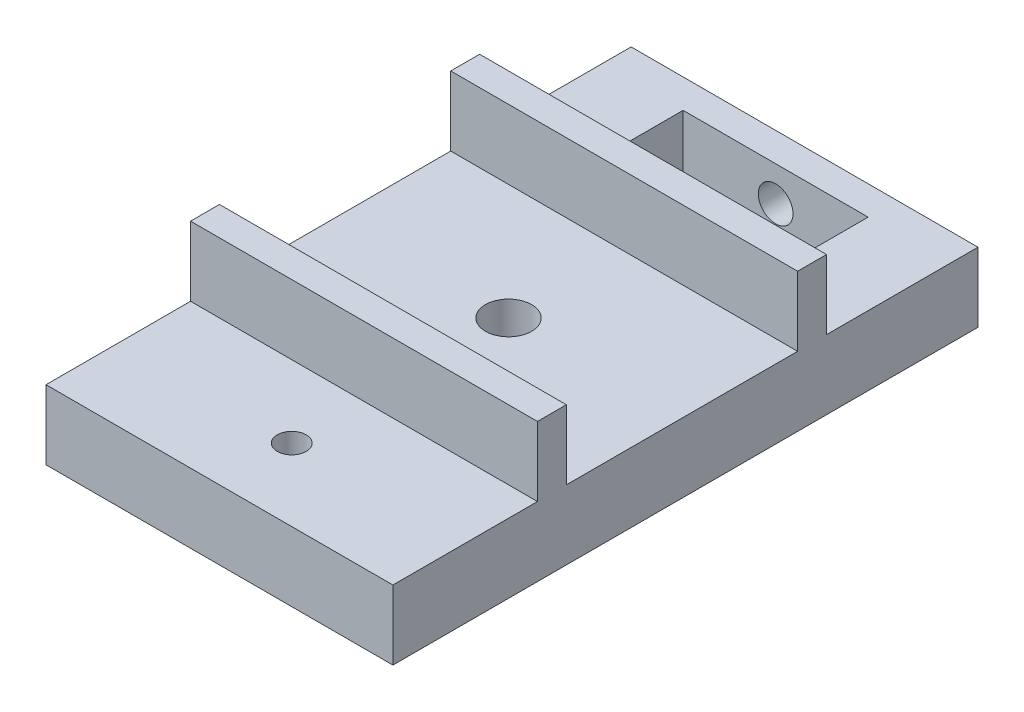
SolidWorks part; units mm, degrees
ref_plane "Front" through (0, 0, 0) normal (0, 0, 1) x (1, 0, 0)
ref_plane "Top" through (0, 0, 0) normal (0, 1, 0) x (1, 0, 0)
ref_plane "Right" through (0, 0, 0) normal (1, 0, 0) x (0, 0, -1)
sketch "Sketch1" plane through (0, 0, 0) normal (0, 1, 0) x (1, 0, 0)
  line L0 (0, -20) -> (0, -22.5)
  line L1 (0, 0) -> (-30, 0)
  line L2 (0, 0) -> (0, -20)
  line L3 (0, -20) -> (-30, -20)
  line L4 (-30, 0) -> (-30, -20)
  line L5 (0, -22.5) -> (-30, -22.5)
  line L6 (-30, -22.5) -> (-30, -20)
  line L7 (0, 0) -> (-7, 0)
  line L8 (-30, 0) -> (0, 0)
  line L9 (-30, 0) -> (-30, 2.5)
  line L10 (-30, 2.5) -> (0, 2.5)
  line L11 (0, 0) -> (0, 2.5)
  line L12 (-30, 0) -> (-23, 0)
  line L13 (-30, 2.5) -> (-30, 13.1)
  line L14 (-30, 13.1) -> (0, 13.1)
  line L15 (0, 13.1) -> (0, 2.5)
  line L16 (0, 13.1) -> (0, 15.6)
  line L17 (0, 15.6) -> (-30, 15.6)
  line L18 (-30, 15.6) -> (-30, 13.1)
  line L19 (-7, 0) -> (-7, 15.6)
  line L20 (-23, 0) -> (-23, 15.6)
  dimension "D1" = 20
  dimension "D2" = 2.5
  dimension "D3" = 2.5
  dimension "D4" = 30
  dimension "D5" = 7
  dimension "D6" = 7
  dimension "D7" = 10.6
  dimension "D8" = 2.5
extrude "Boss-Extrude1" add sketch "Sketch1" along normal blind 6 contours L1 L8 L4 L3 L2 | L6 L5 L0 L3 | L20 L1 L19 L10 | L19 L1 L11 L10 | L19 L10 L15 L14 | L19 L14 L16 L17 | L20 L14 L19 L17 | L14 L20 L17 L18 | L10 L20 L14 L13 | L8 L20 L10 L9 region at (-15, 0, 10) region at (-15, 0, 21.25) region at (-3.5, 0, -1.25) region at (-15, 0, -1.25) region at (-3.5, 0, -7.8) region at (-26.5, 0, -1.25) region at (-3.5, 0, -14.35) region at (-26.5, 0, -7.8) region at (-15, 0, -14.35) region at (-26.5, 0, -14.35)
extrude "Boss-Extrude2" add sketch "Sketch1<3>" along normal blind 12 contours L19 L1 L11 L10 | L20 L1 L19 L10 | L6 L5 L0 L3 | L8 L20 L10 L9 region at (-15, 0, 21.25) region at (-3.5, 0, -1.25) region at (-15, 0, -1.25) region at (-26.5, 0, -1.25)
sketch "Sketch1<3>" plane through (0, 0, 0) normal (0, 1, 0) x (1, 0, 0) same geometry as "Sketch1"
sketch "Sketch3" plane through (0, 0, -15.6) normal (0, 0, -1) x (-1, 0, 0)
  line L0 (30, 3) -> (23, 3)
  line L1 (30, 6) -> (30, 0) construction
  line L2 (23, 3) -> (15, 3)
  circle A0 centre (15, 3) radius 1.5
  dimension "D1" = 7
  dimension "D2" = 8
extrude "Cut-Extrude2" cut sketch "Sketch3" against normal blind 5 contours A0
sketch "Sketch4" plane through (0, 0, -2.5) normal (0, 0, -1) x (-1, 0, 0)
  line L0 (23, 3) -> (15, 3)
  line L1 (23, 6) -> (23, 0) construction
  line L3 (17.8868, 3) -> (16.4434, 5.5)
  line L4 (16.4434, 5.5) -> (13.5566, 5.5)
  line L5 (13.5566, 5.5) -> (12.1132, 3)
  line L6 (12.1132, 3) -> (13.5566, 0.5)
  line L7 (13.5566, 0.5) -> (16.4434, 0.5)
  line L8 (16.4434, 0.5) -> (17.8868, 3)
  circle A0 centre (15, 3) radius 2.5 construction
  dimension "D1" = 8
extrude "Cut-Extrude3" cut sketch "Sketch4" against normal blind 2.5 contours L7 L8 L3 L4 L5 L6 region at (-17.0989, 1.7882, -2.5)
ref_plane "Plane1" through (0, 0, 10) normal (0, 0, -1) x (-1, 0, 0)
sketch "Sketch2" plane through (0, 6, 0) normal (0, 1, 0) x (1, 0, 0)
  line L0 (-30, -10) -> (0, -10)
  line L1 (-30, 0) -> (-30, -20) construction
  line L2 (0, 0) -> (0, -20) construction
  circle A0 centre (-15, -10) radius 2
extrude "Cut-Extrude1" cut sketch "Sketch2" against normal through all contours L0 A0 | L0 A0 region at (-15, 6, 9.1512) region at (-15, 6, 10.8488)
sketch "Sketch5" plane through (0, 0, 0) normal (0, -1, 0) x (1, 0, 0)
  line L0 (-30, 22.5) -> (-25, 22.5)
  line L1 (-30, 22.5) -> (0, 22.5)
  line L2 (-30, 22.5) -> (-30, 32.5)
  line L3 (0, 22.5) -> (0, 32.5)
  line L4 (-30, 32.5) -> (0, 32.5)
  line L5 (-25, 22.5) -> (-25, 32.5)
  line L6 (-25, 32.5) -> (-5, 32.5)
  line L7 (-5, 32.5) -> (-5, 22.5)
  line L8 (-5, 22.5) -> (0, 22.5)
  line L9 (-30, 32.5) -> (-30, 35)
  line L10 (-30, 35) -> (0, 35)
  line L11 (0, 35) -> (0, 32.5)
  line L12 (-15, 35) -> (-15, 22.5)
  circle A0 centre (-15, 28.75) radius 1.25
  line M7 (0, 22.5) -> (-30, 22.5)
  dimension "D1" = 10
  dimension "D2" = 5
  dimension "D3" = 5
  dimension "D4" = 2.5
extrude "Boss-Extrude3" add sketch "Sketch5" against normal blind 6 contours L5 L4 L2 M7 | L11 L10 L9 L4 | L4 L7 L3 M7 | L7 L4 L5 L1 | A0 L12 L4 L5 M7 | L12 L10 L9 L4 region at (-27.5, 0, 27.5) region at (-20.1125, 0, 27.4685) region at (-22.5, 0, 33.75) region at (-9.8875, 0, 27.4685) region at (-2.5, 0, 27.5) region at (-7.5, 0, 33.75)
sketch "Sketch6" plane through (0, 0, 35) normal (0, 0, 1) x (1, 0, 0)
  line L0 (0, 0) -> (0, 3)
  line L1 (0, 6) -> (0, 0) construction
  line L2 (0, 3) -> (0, 1.5)
  line L3 (0, 1.5) -> (-15, 1.5)
  circle A1 centre (-15, 1.5) radius 1.5
